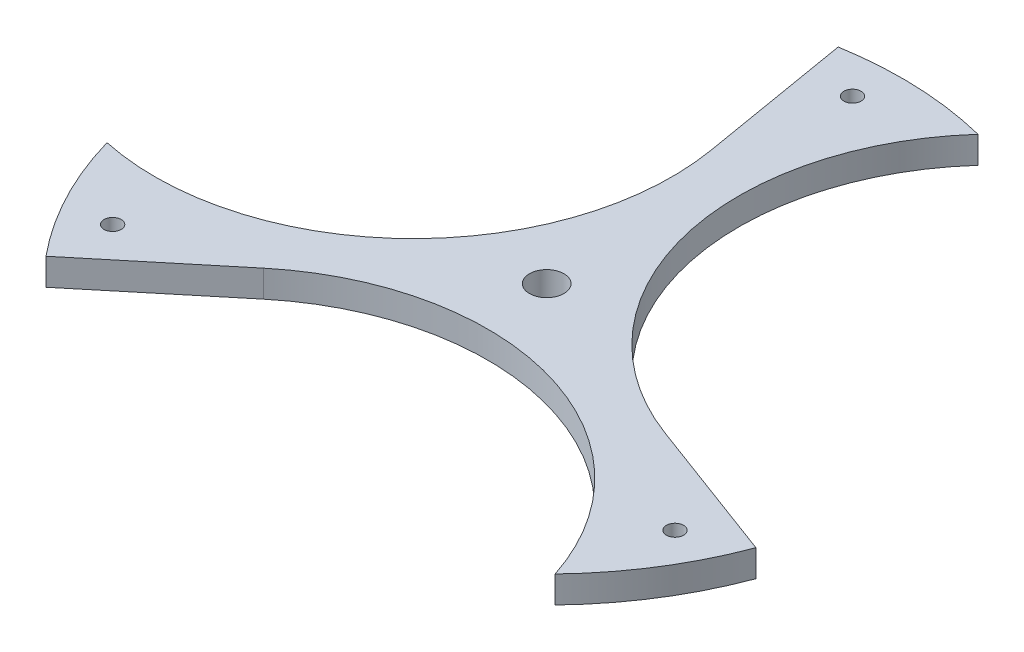
SolidWorks part; units mm, degrees
ref_plane "Front" through (0, 0, 0) normal (0, 0, 1) x (1, 0, 0)
ref_plane "Top" through (0, 0, 0) normal (0, 1, 0) x (1, 0, 0)
ref_plane "Right" through (0, 0, 0) normal (1, 0, 0) x (0, 0, -1)
ref_axis "side-side" through (80.9, 0, 0) along (-1, 0, 0)
ref_axis "up-down" through (0, 50, 0) along (0, -1, 0)
ref_axis "front-back" through (0, 0, -80.9) along (0, 0, 1)
sketch "Sketch3" plane through (0, 0, 0) normal (0, 1, 0) x (1, 0, 0)
  circle A0 centre (0, 0) radius 65.5152 construction
  circle A1 centre (0, 0) radius 65.5152 construction
  circle A2 centre (0, 0) radius 12.7 construction
  circle A3 centre (0, 0) radius 12.7 construction
sketch "Sketch1" plane through (0, 0, 0) normal (0, 1, 0) x (1, 0, 0)
  line L0 (34.7005, -12.9165) -> (61.3996, -22.8547)
  line L1 (0, 0) -> (51.3143, 31.7167) construction
  line L2 (0, 0) -> (1.8103, -60.2978) construction
  line L3 (0, 0) -> (-53.1246, 28.5812) construction
  line L4 (-28.5363, -23.5933) -> (-50.4925, -41.7462)
  line L5 (-6.1642, 36.5098) -> (-10.9071, 64.6009)
  line L6 (0, 0) -> (-1.7435, 58.0732) construction
  line L7 (0, 0) -> (51.1646, -27.5267) construction
  line L8 (0, 0) -> (-49.4211, -30.5465) construction
  circle A0 centre (0, 0) radius 65.5152 construction
  arc A1 (15.8978, 63.5571) -> (-10.9071, 64.6009) centre (0, 0) ccw
  circle A2 centre (51.3143, 31.7167) radius 47.625 construction
  arc A3 (15.8978, 63.5571) -> (34.7005, -12.9165) centre (51.3143, 31.7167) ccw
  circle A4 centre (0, 0) radius 12.7 construction
  circle A5 centre (0, 0) radius 12.7 construction
  arc A6 (47.0931, -45.5464) -> (-28.5363, -23.5933) centre (1.8103, -60.2978) ccw
  arc A7 (-62.9909, -18.0107) -> (-6.1642, 36.5098) centre (-53.1246, 28.5812) ccw
  arc A8 (47.0931, -45.5464) -> (61.3996, -22.8547) centre (0, 0) ccw
  arc A9 (-62.9909, -18.0107) -> (-50.4925, -41.7462) centre (0, 0) ccw
  circle A10 centre (0, 0) radius 3.175
  circle A11 centre (-1.7435, 58.0732) radius 1.5875
  circle A12 centre (-49.4211, -30.5465) radius 1.5875
  circle A13 centre (51.1646, -27.5267) radius 1.5875
  dimension "D3" = 6.35
  dimension "D4" = 3.175
  dimension "D1" = 120
  dimension "D2" = 120
  dimension "D5" = 58.0732
  dimension "D6" = 120
  dimension "D7" = 120
extrude "Boss-Extrude1" add sketch "Sketch1" along normal mid plane 4.953
sketch "Sketch2" plane through (0, 0, 0) normal (0, 0, 1) x (1, 0, 0)
  line L0 (51.3143, -50) -> (51.3143, 50) construction
  arc A0 (0, 0) -> (51.3143, 51.3143) centre (51.3143, 0) cw
